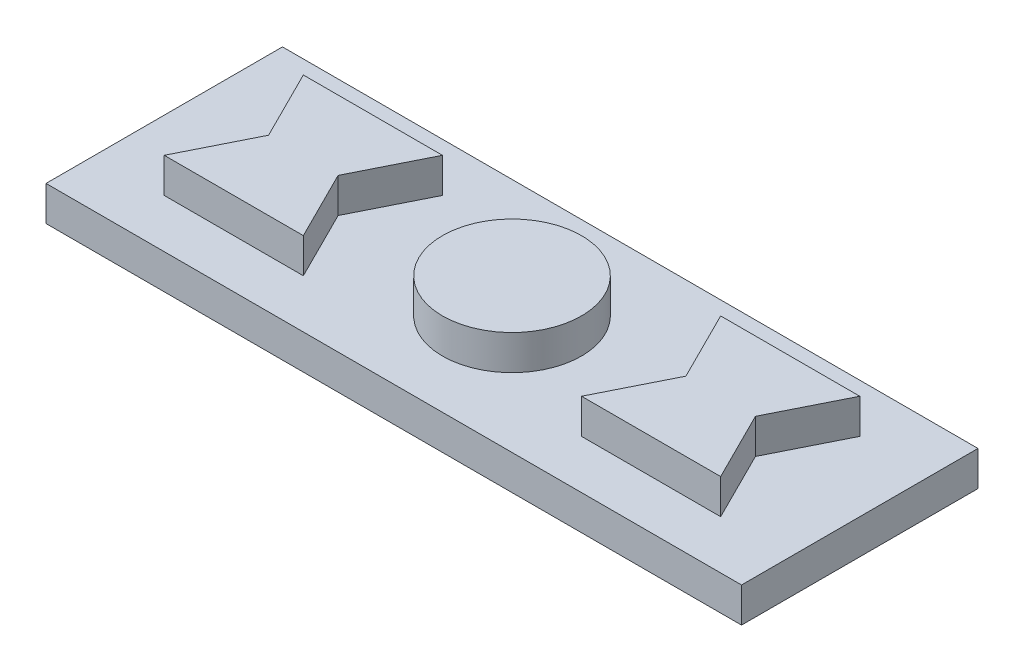
SolidWorks part; units mm, degrees
ref_plane "前视基准面" through (0, 0, 0) normal (0, 0, 1) x (1, 0, 0)
ref_plane "上视基准面" through (0, 0, 0) normal (0, 1, 0) x (1, 0, 0)
ref_plane "右视基准面" through (0, 0, 0) normal (1, 0, 0) x (0, 0, -1)
other "Configuration Table"
sketch "草图1" plane through (0, 0, 0) normal (0, 1, 0) x (1, 0, 0)
  line L0 (0, 0) -> (-50, 0) construction
  line L1 (-50, 17) -> (50, 17)
  line L2 (-50, 17) -> (-50, -17)
  line L3 (-50, -17) -> (50, -17)
  line L4 (50, 17) -> (50, -17)
  line L5 (-50, 17) -> (50, -17) construction
  line L6 (-50, -17) -> (50, 17) construction
  line L7 (-40, 10) -> (-20, 10)
  line L8 (-20, 10) -> (-25, 0)
  line L9 (-40, 10) -> (-35, 0)
  line L10 (-30, 10) -> (-30, 0) construction
  line L11 (-40, -10) -> (-35, 0)
  line L12 (-40, -10) -> (-20, -10)
  line L13 (-20, -10) -> (-25, 0)
  line L14 (0, 0) -> (0, -17) construction
  line L15 (40, 10) -> (20, 10)
  line L16 (40, 10) -> (35, 0)
  line L17 (20, 10) -> (25, 0)
  line L18 (20, -10) -> (25, 0)
  line L19 (40, -10) -> (20, -10)
  line L20 (40, -10) -> (35, 0)
  circle A0 centre (0, 0) radius 10
  point P0 (0, 0)
  dimension "D3" = 20
  dimension "D1" = 34
  dimension "D2" = 100
  dimension "D4" = 10
  dimension "D5" = 20
  dimension "D6" = 20
  dimension "D7" = 30
extrude "凸台-拉伸1" add sketch "草图1" along normal blind 5
extrude "凸台-拉伸2" add sketch "草图1<2>" along normal blind 10 contours L12 L13 L8 L7 L9 L11 | A0 | L19 L20 L16 L15 L17 L18 region at (-30, 0, 0) region at (30, 0, 0) region at (0, 0, 0)
sketch "草图1<2>" plane through (0, 0, 0) normal (0, 1, 0) x (1, 0, 0) same geometry as "草图1"
